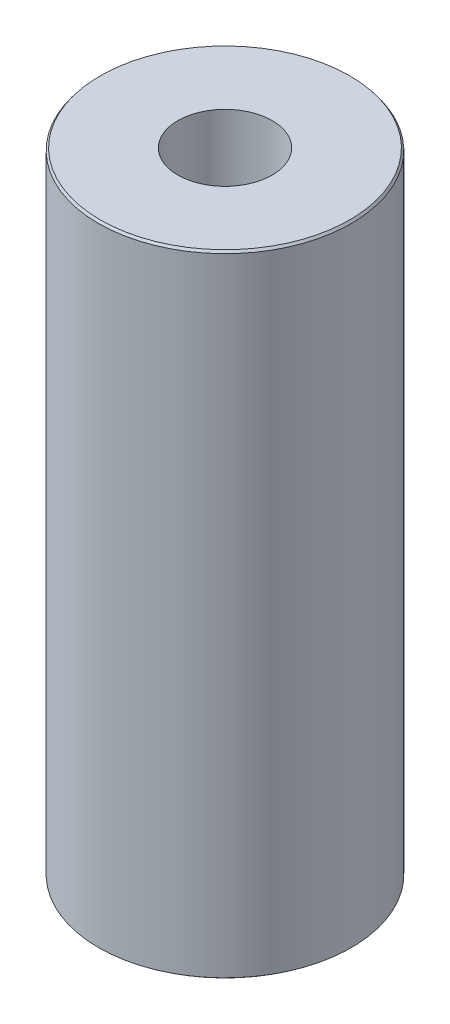
SolidWorks part; units mm, degrees
ref_plane "Front Plane" through (0, 0, 0) normal (0, 0, 1) x (1, 0, 0)
ref_plane "Top Plane" through (0, 0, 0) normal (0, 1, 0) x (1, 0, 0)
ref_plane "Right Plane" through (0, 0, 0) normal (1, 0, 0) x (0, 0, -1)
sketch "Sketch1" plane through (0, 0, 0) normal (0, 1, 0) x (1, 0, 0)
  circle A0 centre (0, 0) radius 45
  dimension "SHAFT_OD" = 90
extrude "Boss-Extrude1" add sketch "Sketch1" along normal blind 224.5491
sketch "Sketch2" plane through (0, 0, 0) normal (0, 1, 0) x (1, 0, 0)
  circle A0 centre (0, 0) radius 16.7922
  dimension "BORE_D" = 33.5844
extrude "Cut-Extrude1" cut sketch "Sketch2" along normal through all
chamfer "Chamfer1" distance 0.8003 angle 37.172 2 edges at (0, 224.5491, 45) (0, 0, 45) first distance on face at (0, 224.5491, 45) first distance on face at (0, 0, 16.7922)
